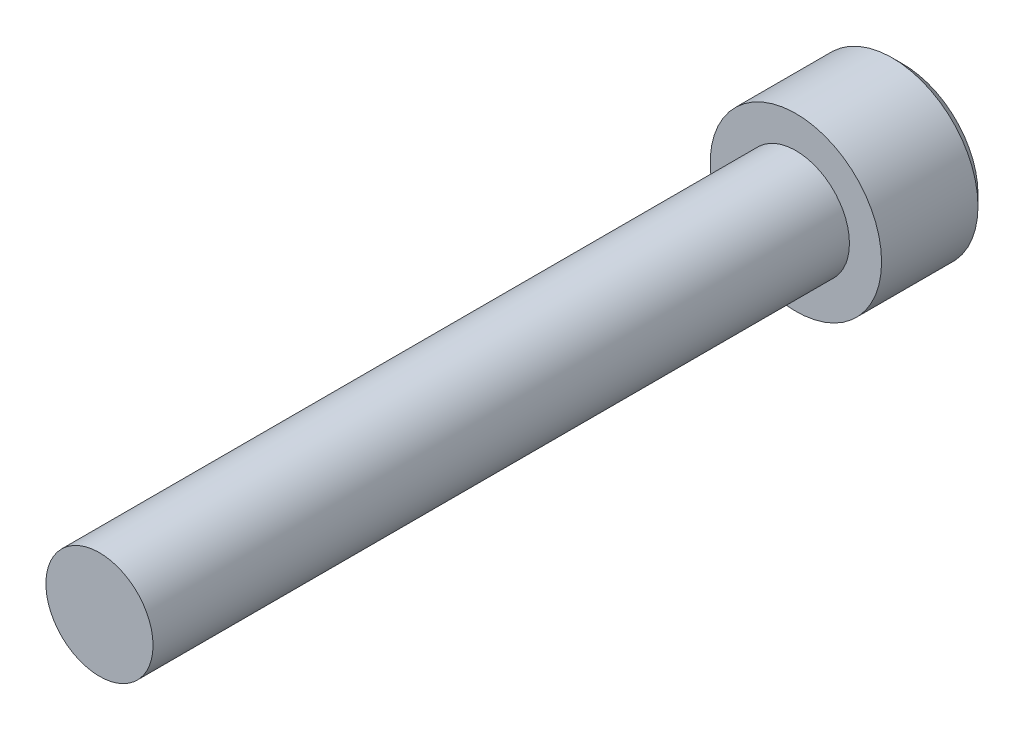
SolidWorks part; units mm, degrees
ref_plane "前视基准面" through (0, 0, 0) normal (0, 0, 1) x (1, 0, 0)
ref_plane "上视基准面" through (0, 0, 0) normal (0, 1, 0) x (1, 0, 0)
ref_plane "右视基准面" through (0, 0, 0) normal (1, 0, 0) x (0, 0, -1)
sketch "草图1" plane through (0, 0, 0) normal (0, 0, 1) x (1, 0, 0)
  circle A0 centre (0, 0) radius 8
  circle A1 centre (0, 0) radius 5
  dimension "D1" = 16
  dimension "D2" = 10
extrude "凸台-拉伸1" add sketch "草图1" along normal blind 65 contours A1 region at (0, 0, 0)
extrude "凸台-拉伸2" add sketch "草图1<3>" against normal blind 10 contours A1 | A0 A1 region at (-7.7737, 0, 0) region at (0, 0, 0)
sketch "草图1<3>" plane through (0, 0, 0) normal (0, 0, 1) x (1, 0, 0) same geometry as "草图1"
chamfer "倒角1" distance 1 angle 45 1 edges at (8, 0, -10)
